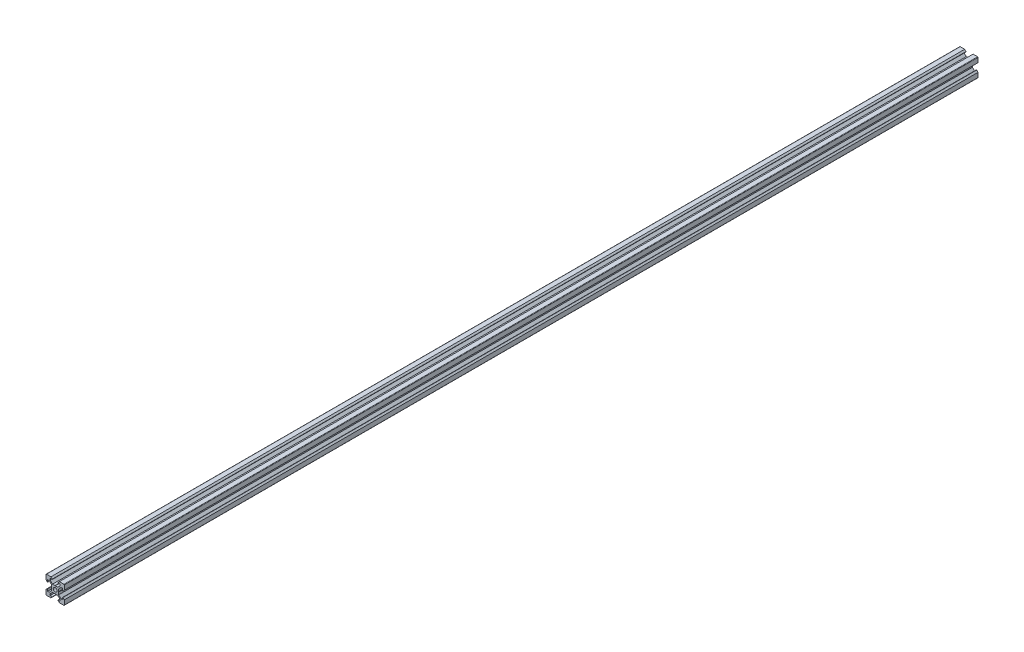
SolidWorks part; units mm, degrees
material "6061-T6 (SS)"
ref_plane "Front Plane" through (0, 0, 0) normal (0, 0, 1) x (1, 0, 0)
ref_plane "Top Plane" through (0, 0, 0) normal (0, 1, 0) x (1, 0, 0)
ref_plane "Right Plane" through (0, 0, 0) normal (1, 0, 0) x (0, 0, -1)
sketch "Sketch1" plane through (0, 0, 0) normal (0, 0, 1) x (1, 0, 0)
  line L1 (9.5, -10) -> (-9.5, -10)
  line L2 (10, -9.5) -> (10, 9.5)
  line L3 (9.5, 10) -> (-9.5, 10)
  line L4 (-10, -9.5) -> (-10, 9.5)
  line L5 (10, -10) -> (-10, 10) construction
  line L6 (10, 10) -> (-10, -10) construction
  circle A0 centre (0, 0) radius 2.1
  arc A1 (-9.5, 10) -> (-10, 9.5) centre (-9.5, 9.5) ccw
  arc A2 (10, 9.5) -> (9.5, 10) centre (9.5, 9.5) ccw
  arc A3 (9.5, -10) -> (10, -9.5) centre (9.5, -9.5) ccw
  arc A4 (-9.5, -10) -> (-10, -9.5) centre (-9.5, -9.5) cw
  point P0 (0, 0)
  line B0 (0, 0) -> (0, 10) construction
  line B1 (0, 3.69) -> (-0.21, 3.9)
  line B2 (-0.21, 3.9) -> (-2.8393, 3.9)
  line B3 (-2.8393, 3.9) -> (-5.5, 6.5607)
  line B4 (-5.5, 6.5607) -> (-5.5, 8.2)
  line B5 (-5.5, 8.2) -> (-3.125, 8.2)
  line B6 (-3.125, 8.2) -> (-3.125, 8.545)
  line B7 (-3.125, 8.545) -> (-4.58, 10)
  line B8 (-4.58, 10) -> (4.58, 10)
  line B9 (0, 0) -> (-5.9132, 5.9132) construction
  line B10 (3.125, 8.545) -> (4.58, 10)
  line B11 (3.125, 8.2) -> (3.125, 8.545)
  line B12 (5.5, 8.2) -> (3.125, 8.2)
  line B13 (5.5, 6.5607) -> (5.5, 8.2)
  line B14 (2.8393, 3.9) -> (5.5, 6.5607)
  line B15 (0.21, 3.9) -> (2.8393, 3.9)
  line B16 (0, 3.69) -> (0.21, 3.9)
  line B17 (0, 0) -> (-10, 0) construction
  line B18 (-3.69, 0) -> (-3.9, -0.21)
  line B19 (-3.9, -0.21) -> (-3.9, -2.8393)
  line B20 (-3.9, -2.8393) -> (-6.5607, -5.5)
  line B21 (-6.5607, -5.5) -> (-8.2, -5.5)
  line B22 (-8.2, -5.5) -> (-8.2, -3.125)
  line B23 (-8.2, -3.125) -> (-8.545, -3.125)
  line B24 (-8.545, -3.125) -> (-10, -4.58)
  line B25 (-10, -4.58) -> (-10, 4.58)
  line B26 (0, 0) -> (-5.9132, -5.9132) construction
  line B27 (-8.545, 3.125) -> (-10, 4.58)
  line B28 (-8.2, 3.125) -> (-8.545, 3.125)
  line B29 (-8.2, 5.5) -> (-8.2, 3.125)
  line B30 (-6.5607, 5.5) -> (-8.2, 5.5)
  line B31 (-3.9, 2.8393) -> (-6.5607, 5.5)
  line B32 (-3.9, 0.21) -> (-3.9, 2.8393)
  line B33 (-3.69, 0) -> (-3.9, 0.21)
  line B34 (0, 0) -> (0, -10) construction
  line B35 (0, -3.69) -> (0.21, -3.9)
  line B36 (0.21, -3.9) -> (2.8393, -3.9)
  line B37 (2.8393, -3.9) -> (5.5, -6.5607)
  line B38 (5.5, -6.5607) -> (5.5, -8.2)
  line B39 (5.5, -8.2) -> (3.125, -8.2)
  line B40 (3.125, -8.2) -> (3.125, -8.545)
  line B41 (3.125, -8.545) -> (4.58, -10)
  line B42 (4.58, -10) -> (-4.58, -10)
  line B43 (0, 0) -> (5.9132, -5.9132) construction
  line B44 (-3.125, -8.545) -> (-4.58, -10)
  line B45 (-3.125, -8.2) -> (-3.125, -8.545)
  line B46 (-5.5, -8.2) -> (-3.125, -8.2)
  line B47 (-5.5, -6.5607) -> (-5.5, -8.2)
  line B48 (-2.8393, -3.9) -> (-5.5, -6.5607)
  line B49 (-0.21, -3.9) -> (-2.8393, -3.9)
  line B50 (0, -3.69) -> (-0.21, -3.9)
  line B51 (0, 0) -> (10, 0) construction
  line B52 (3.69, 0) -> (3.9, 0.21)
  line B53 (3.9, 0.21) -> (3.9, 2.8393)
  line B54 (3.9, 2.8393) -> (6.5607, 5.5)
  line B55 (6.5607, 5.5) -> (8.2, 5.5)
  line B56 (8.2, 5.5) -> (8.2, 3.125)
  line B57 (8.2, 3.125) -> (8.545, 3.125)
  line B58 (8.545, 3.125) -> (10, 4.58)
  line B59 (10, 4.58) -> (10, -4.58)
  line B60 (0, 0) -> (5.9132, 5.9132) construction
  line B61 (8.545, -3.125) -> (10, -4.58)
  line B62 (8.2, -3.125) -> (8.545, -3.125)
  line B63 (8.2, -5.5) -> (8.2, -3.125)
  line B64 (6.5607, -5.5) -> (8.2, -5.5)
  line B65 (3.9, -2.8393) -> (6.5607, -5.5)
  line B66 (3.9, -0.21) -> (3.9, -2.8393)
  line B67 (3.69, 0) -> (3.9, -0.21)
  dimension "D1" = 4.2
  dimension "D2" = 20
sketch_block_instance "V Slot 1-4"
sketch_block "V Slot 1" parameters "D1"=10, "D2"=11, "D3"=4.3, "D4"=1.8, "D5"=0.21, "D6"=45, "D7"=9.16, "D8"=1.5, "D9"=6.25
sketch_block_instance "V Slot 1-5"
sketch_block_instance "V Slot 1-6"
sketch_block_instance "V Slot 1-7" parameters "D1"=31.2546, "D3"=0.5, "D2"=9.6469
extrude "Boss-Extrude1" add sketch "Sketch1" along normal blind 1000 contours B67 B52 B53 B54 B55 B56 B57 B58 L2 A2 L3 B10 B11 B12 B13 B14 B15 B16 B1 B2 B3 B4 B5 B6 B7 A1 L4 B27 B28 B29 B30 B31 B32 B33 B18 B19 B20 B21 B22 B23 B24 A4 L1 B44 B45 B46 B47 B48 B49 region at (7.04, -9.7172, 0)
